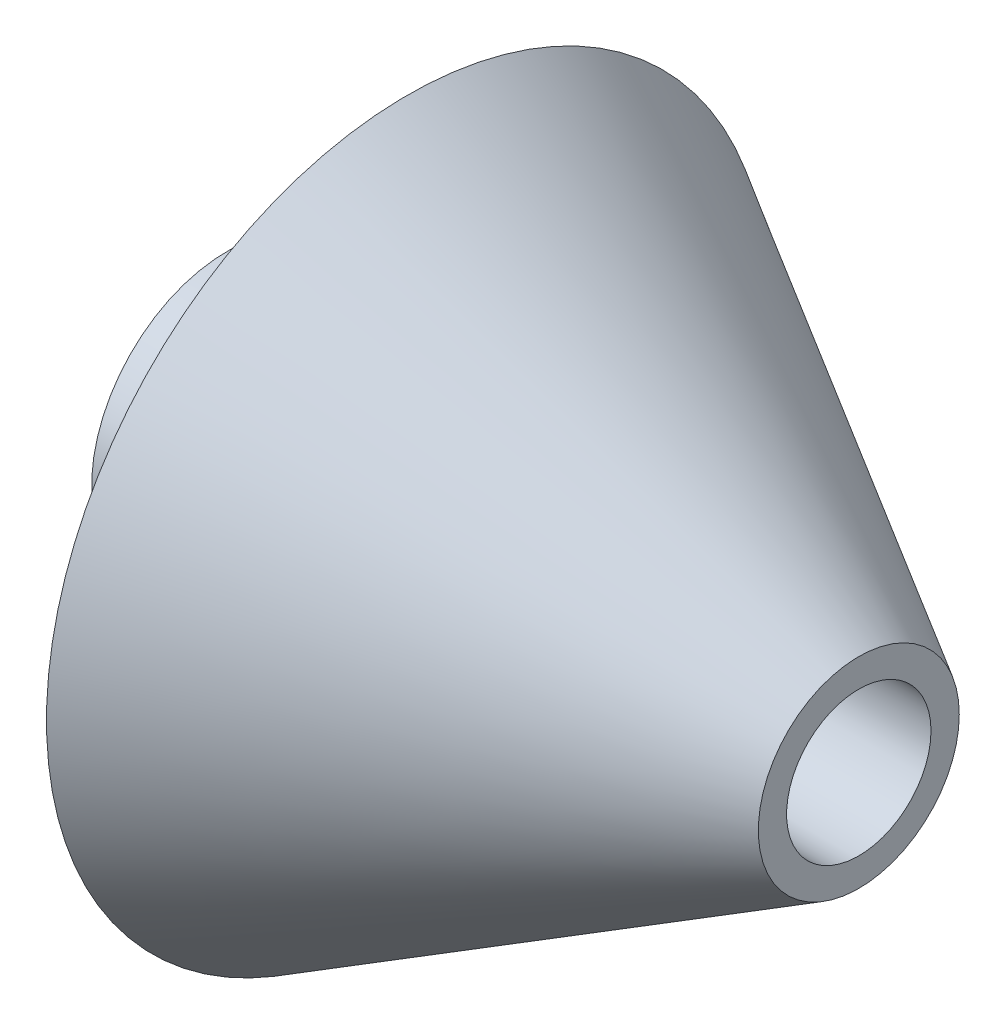
SolidWorks part; units mm, degrees
ref_plane "Alzado" through (0, 0, 0) normal (0, 0, 1) x (1, 0, 0)
ref_plane "Planta" through (0, 0, 0) normal (0, 1, 0) x (1, 0, 0)
ref_plane "Vista lateral" through (0, 0, 0) normal (1, 0, 0) x (0, 0, -1)
sketch "Croquis1" plane through (0, 0, 0) normal (1, 0, 0) x (0, 0, -1)
  line L0 (0, 7.5) -> (0, -7.5) construction
  line L1 (-7.5, 0) -> (7.5, 0) construction
  circle A0 centre (0, 0) radius 7.5
  dimension "D1" = 15
extrude "Saliente-Extruir1" add sketch "Croquis1" along normal blind 10
sketch "Croquis2" plane through (10, 0, 0) normal (1, 0, 0) x (0, 0, -1)
  circle A0 centre (0, 0) radius 20
  dimension "D1" = 40
extrude "Saliente-Extruir2" add sketch "Croquis2" along normal blind 25 draft 30
sketch "Croquis3" plane through (35, 0, 0) normal (1, 0, 0) x (0, 0, -1)
  circle A0 centre (0, 0) radius 4
  dimension "D1" = 8
extrude "Cortar-Extruir2" cut sketch "Croquis3" against normal blind 70
hole_wizard "Taladro de margen para M41" positions "Croquis3D1" profile "Croquis4" hole size "M4" standard "ISO" end condition up to next
sketch3d "Croquis3D1"
  point P0 (5, 7.4812, -0.5307)
  dimension "D1" = 5
sketch "Croquis4" plane through (5, 7.4812, -0.5307) normal (1, 0, 0) x (0, 0.0708, 0.9975)
  line L0 (0, 0) -> (0, 3.5)
  line L1 (0, 3.5) -> (2.25, 3.5)
  line L2 (2.25, 3.5) -> (2.25, 0)
  line L5 (2.25, 0) -> (0, 0)
  line L11 (0, -6.35) -> (0, 107.95) construction
  dimension "Diámetro de taladro hasta el siguiente" = 4.5
  dimension "Profundidad de taladro hasta el siguiente" = 3.5
